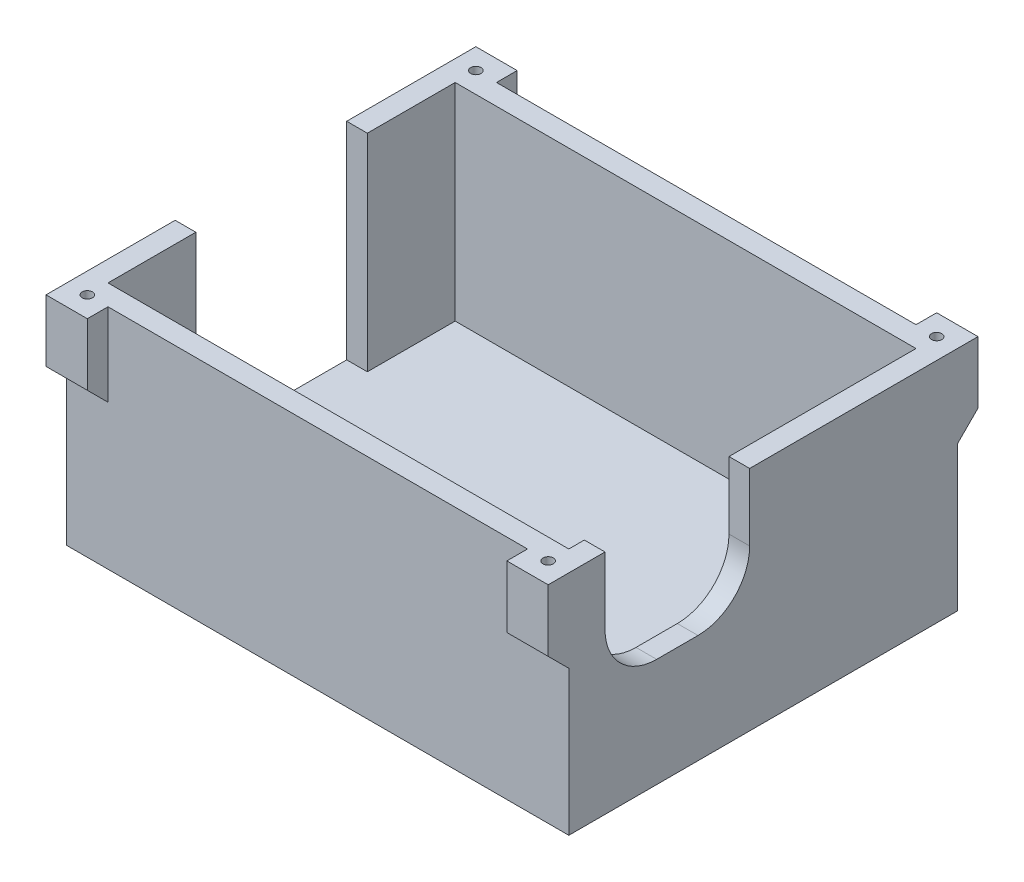
SolidWorks part; units mm, degrees
ref_plane "Front Plane" through (0, 0, 0) normal (0, 0, 1) x (1, 0, 0)
ref_plane "Top Plane" through (0, 0, 0) normal (0, 1, 0) x (1, 0, 0)
ref_plane "Right Plane" through (0, 0, 0) normal (1, 0, 0) x (0, 0, -1)
sketch "Sketch1" plane through (0, 0, 0) normal (0, 1, 0) x (1, 0, 0)
  line L0 (-0.3, 33.3) -> (44.3, 33.3)
  line L1 (0, 0) -> (44, 0)
  line L2 (0, 0) -> (0, 33)
  line L3 (0, 33) -> (44, 33)
  line L4 (44, 0) -> (44, 33)
  line L5 (44.3, -0.3) -> (44.3, 33.3)
  line L6 (-0.3, -0.3) -> (44.3, -0.3)
  line L7 (-0.3, -0.3) -> (-0.3, 33.3)
  line L8 (-2.3, 35.3) -> (46.3, 35.3)
  line L9 (46.3, -2.3) -> (46.3, 35.3)
  line L10 (-2.3, -2.3) -> (46.3, -2.3)
  line L11 (-2.3, -2.3) -> (-2.3, 35.3)
  dimension "D1" = 44
  dimension "D2" = 33
  dimension "D3" = 0.3
  dimension "D4" = 2
extrude "Boss-Extrude1" add sketch "Sketch1" along normal blind 2 contours L11 L10 L9 L8 L6 L7 L0 L5 | L1 L4 L3 L2 | L7 L6 L5 L0 L4 L1 L2 L3 region at (22, 0, -33.2442) region at (22, 0, -16.5) region at (22, 0, -34.6855)
extrude "Boss-Extrude2" add sketch "Sketch1<3>" along normal offset from surface (22 mm away) 20 contours L11 L10 L9 L8 L6 L7 L0 L5 region at (22, 0, -34.6855) up to face at (22, 2, -16.5) offset beyond the face yes
sketch "Sketch1<3>" plane through (0, 0, 0) normal (0, 1, 0) x (1, 0, 0) same geometry as "Sketch1"
sketch "Sketch2" plane through (0, 22, 0) normal (0, 1, 0) x (1, 0, 0)
  line L0 (-0.3, -0.3) -> (-0.3, 33.3) construction
  line L1 (-0.3, 8.2) -> (-2.3, 8.2)
  line L2 (-0.3, 8.2) -> (-0.3, 24.8)
  line L3 (-0.3, 24.8) -> (-2.3, 24.8)
  line L4 (-2.3, 8.2) -> (-2.3, 24.8)
  line L5 (-2.3, -2.3) -> (-2.3, 35.3) construction
  line L6 (-0.3, -0.3) -> (44.3, -0.3) construction
  line L7 (44.3, 33.3) -> (-0.3, 33.3) construction
  dimension "D1" = 8.5
  dimension "D2" = 8.5
extrude "Cut-Extrude1" cut sketch "Sketch2" against normal up to surface (20 mm away) up to face at (22, 2, -16.5)
sketch "Sketch3" plane through (0, 22, 0) normal (0, 1, 0) x (1, 0, 0)
  line L0 (44.3, 33.3) -> (44.3, -0.3) construction
  line L1 (44.3, 1.2) -> (46.3, 1.2)
  line L2 (44.3, 1.2) -> (44.3, 15.2)
  line L3 (44.3, 15.2) -> (46.3, 15.2)
  line L4 (46.3, 1.2) -> (46.3, 15.2)
  line L5 (46.3, -2.3) -> (46.3, 35.3) construction
  line L7 (-0.3, -0.3) -> (44.3, -0.3) construction
  point P10 (44.3, 8.2)
  dimension "D1" = 14
  dimension "D2" = 8.5
extrude "Cut-Extrude2" cut sketch "Sketch3" against normal offset from surface (11.5 mm away) 8.5 up to face at (10.35, 2, -16.5)
fillet "Fillet1" radius 5 2 edges at (45.3, 10.5, -15.2) (45.3, 10.5, -1.2)
sketch "Sketch4" plane through (0, 22, 0) normal (0, 1, 0) x (1, 0, 0)
  line L1 (46.3, -2.3) -> (42.3, -2.3)
  line L2 (46.3, -2.3) -> (46.3, -4.3)
  line L3 (46.3, -4.3) -> (42.3, -4.3)
  line L4 (42.3, -2.3) -> (42.3, -4.3)
  line L5 (-2.3, -2.3) -> (1.7, -2.3)
  line L6 (-2.3, -2.3) -> (-2.3, -4.3)
  line L7 (-2.3, -4.3) -> (1.7, -4.3)
  line L8 (1.7, -2.3) -> (1.7, -4.3)
  line L9 (-2.3, 35.3) -> (1.7, 35.3)
  line L10 (-2.3, 35.3) -> (-2.3, 37.3)
  line L11 (-2.3, 37.3) -> (1.7, 37.3)
  line L12 (1.7, 35.3) -> (1.7, 37.3)
  line L13 (46.3, 35.3) -> (42.3, 35.3)
  line L14 (46.3, 35.3) -> (46.3, 37.3)
  line L15 (46.3, 37.3) -> (42.3, 37.3)
  line L16 (42.3, 35.3) -> (42.3, 37.3)
  dimension "D1" = 2
  dimension "D2" = 4
  dimension "D3" = 2
  dimension "D4" = 4
  dimension "D5" = 2
  dimension "D6" = 4
  dimension "D7" = 4
  dimension "D8" = 2
extrude "Boss-Extrude3" add sketch "Sketch4" against normal blind 6
chamfer "Chamfer1" distance 2 angle 45 4 edges at (-0.3, 16, 2.3) (44.3, 16, 2.3) (-0.3, 16, -35.3) (44.3, 16, -35.3)
sketch "Sketch5" plane through (0, 22, 0) normal (0, 1, 0) x (1, 0, 0)
  line L0 (46.3, 37.3) -> (42.3, 37.3) construction
  line L1 (-2.3, -4.3) -> (1.7, -4.3) construction
  line L2 (-2.3, -4.3) -> (-2.3, 8.2) construction
  circle A0 centre (44.3, -2.3) radius 0.5
  circle A1 centre (-0.3, -2.3) radius 0.5
  circle A2 centre (-0.3, 35.3) radius 0.5
  circle A3 centre (44.3, 35.3) radius 0.5
  point P11 (0, 0)
  point P12 (0, 0)
  point P13 (0, 0)
  point P14 (0, 0)
  point P15 (0, 0)
  point P16 (0, 0)
  dimension "D1" = 1
  dimension "D2" = 1
  dimension "D3" = 1
  dimension "D4" = 1
  dimension "D5" = 2
  dimension "D6" = 2
  dimension "D7" = 2
  dimension "D8" = 2
extrude "Cut-Extrude4" cut sketch "Sketch5" against normal blind 6
